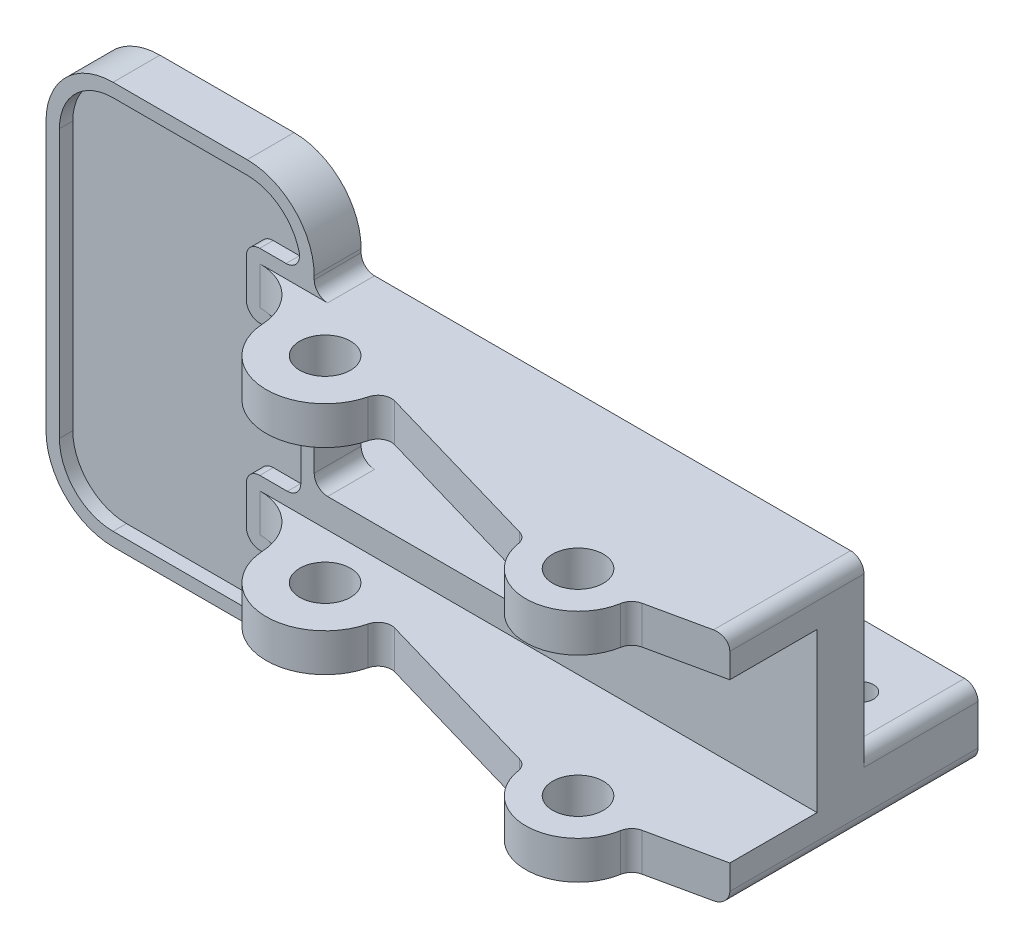
SolidWorks part; units mm, degrees
ref_plane "Front Plane" through (0, 0, 0) normal (0, 0, 1) x (1, 0, 0)
ref_plane "Top Plane" through (0, 0, 0) normal (0, 1, 0) x (1, 0, 0)
ref_plane "Right Plane" through (0, 0, 0) normal (1, 0, 0) x (0, 0, -1)
sketch "Sketch1" plane through (0, 0, 0) normal (0, 0, 1) x (1, 0, 0)
  line L1 (57.15, -22.225) -> (-57.15, -22.225)
  line L2 (57.15, -22.225) -> (57.15, 22.225)
  line L3 (57.15, 22.225) -> (-57.15, 22.225)
  line L4 (-57.15, -22.225) -> (-57.15, 22.225)
  line L5 (57.15, -22.225) -> (-57.15, 22.225) construction
  line L6 (57.15, 22.225) -> (-57.15, -22.225) construction
  point P0 (0, 0)
  dimension "D1" = 44.45
  dimension "D2" = 114.3
extrude "Boss-Extrude1" add sketch "Sketch1" along normal blind 62.23
sketch "Sketch2" plane through (0, 0, 62.23) normal (0, 0, 1) x (1, 0, 0)
  line L0 (-57.15, 22.225) -> (-57.15, -22.225) construction
  line L1 (57.15, -15.025) -> (-57.15, -15.025)
  line L2 (57.15, -15.025) -> (57.15, 15.025)
  line L3 (57.15, 15.025) -> (-57.15, 15.025)
  line L4 (-57.15, -15.025) -> (-57.15, 15.025)
  line L5 (57.15, -15.025) -> (-57.15, 15.025) construction
  line L6 (57.15, 15.025) -> (-57.15, -15.025) construction
  line L7 (57.15, 22.225) -> (-57.15, 22.225) construction
  point P0 (0, 0)
  dimension "D1" = 7.2
extrude "Cut-Extrude2" cut sketch "Sketch2" against normal blind 31.75
sketch "Sketch3" plane through (0, 0, 0) normal (0, 0, -1) x (-1, 0, 0)
  line L0 (-57.15, -22.225) -> (-57.15, 22.225) construction
  line L1 (57.15, 22.225) -> (-57.15, 22.225)
  line L2 (57.15, 22.225) -> (57.15, -9.525)
  line L3 (57.15, -9.525) -> (-57.15, -9.525)
  line L4 (-57.15, 22.225) -> (-57.15, -9.525)
  line L5 (57.15, -22.225) -> (-57.15, -22.225) construction
  dimension "D1" = 12.7
extrude "Cut-Extrude3" cut sketch "Sketch3" against normal blind 21.59
sketch "Sketch5" plane through (0, -22.225, 0) normal (0, -1, 0) x (1, 0, 0)
  line L0 (-3.81, 12.06) -> (46.99, 12.06) construction
  line L1 (57.15, 21.59) -> (-57.15, 21.59) construction
  line L2 (57.15, 62.23) -> (57.15, 0) construction
  circle A0 centre (-3.81, 12.06) radius 2.415
  circle A1 centre (46.99, 12.06) radius 2.415
  dimension "D3" = 4.83
  dimension "D4" = 10.16
  dimension "D1" = 9.53
  dimension "D2" = 50.8
extrude "Cut-Extrude4" cut sketch "Sketch5" against normal blind 25.4
sketch "Sketch6" plane through (0, 0, 21.59) normal (0, 0, -1) x (-1, 0, 0)
  line L0 (-49.405, -9.525) -> (6.225, -9.525) construction
  line L1 (-49.405, -9.525) -> (-49.405, -22.225) construction
  line L2 (6.225, -22.225) -> (6.225, -9.525) construction
  line L3 (-57.15, -9.525) -> (57.15, -9.525) construction
  line L6 (-29.083, 1.651) -> (-29.083, 6.477) construction
  line L7 (-22.4401, 6.477) -> (-22.4401, 1.651) construction
  line L8 (-29.083, 6.477) -> (-14.097, 6.477) construction
  line L9 (-19.177, 1.651) -> (-29.083, 1.651) construction
  circle A1 centre (-26.8605, 4.064) radius 2.2225
  dimension "D3" = 4.445
extrude "Cut-Extrude5" cut sketch "Sketch6" against normal blind 5.08
sketch "Sketch7" plane through (0, -22.225, 0) normal (0, -1, 0) x (1, 0, 0)
  line L0 (57.15, 62.23) -> (57.15, 0) construction
  line L1 (-57.15, 0) -> (57.15, 0) construction
  circle A0 centre (31.75, 50.36) radius 4.8
  circle A1 centre (-27.14, 39.37) radius 4.8
  dimension "D1" = 9.6
  dimension "D2" = 25.4
  dimension "D3" = 39.37
  dimension "D4" = 9.6
  dimension "D5" = 58.89
  dimension "D6" = 10.99
extrude "Cut-Extrude6" cut sketch "Sketch7" against normal up to surface (44.45 mm away) up to face at (0, 22.225, 41.91)
sketch "Sketch9" plane through (0, 0, 30.48) normal (0, 0, 1) x (1, 0, 0)
  line L5 (57.15, 15.025) -> (-57.15, 15.025) construction
  line L6 (-38.1, 15.025) -> (6.35, 15.025)
  line L7 (-38.1, 15.025) -> (-38.1, -15.025)
  line L8 (-38.1, -15.025) -> (6.35, -15.025)
  line L9 (6.35, 15.025) -> (6.35, -15.025)
  line L10 (-57.15, -15.025) -> (57.15, -15.025) construction
  line L11 (-57.15, 15.025) -> (-57.15, -15.025) construction
  line L12 (57.15, -15.025) -> (57.15, 15.025) construction
  dimension "D1" = 50.8
  dimension "25in" = 19.05
extrude "Cut-Extrude7" cut sketch "Sketch9" against normal through all both and the other way through all
sketch "Sketch16" plane through (0, -22.225, 0) normal (0, -1, 0) x (1, 0, 0)
  line L1 (-38.1, 30.48) -> (-57.15, 30.48) construction
  line L8 (-57.15, 62.23) -> (57.15, 62.23)
  line L9 (57.15, 62.23) -> (57.15, 47.0103)
  line L10 (57.15, 62.23) -> (57.15, 0) construction
  line L11 (-15.99, 39.37) -> (21.87, 50.36)
  line L12 (41.63, 50.36) -> (57.15, 47.0103)
  line L13 (-48.4121, 30.48) -> (-57.15, 30.48)
  line L15 (-57.15, 30.48) -> (-57.15, 62.23)
  arc A2 (41.63, 50.36) -> (21.87, 50.36) centre (31.75, 50.36) ccw
  arc A3 (-15.99, 39.37) -> (-38.2702, 40.0345) centre (-27.14, 39.37) ccw
  circle A4 centre (-27.14, 39.37) radius 4.8 construction
  circle A5 centre (31.75, 50.36) radius 4.8 construction
  arc A6 (-48.4121, 30.48) -> (-38.2702, 40.0345) centre (-48.4121, 40.64) ccw
  dimension "D1" = 6.35
  dimension "D2" = 5.08
  dimension "D3" = 10.16
extrude "Cut-Extrude8" cut sketch "Sketch16" against normal through all
fillet "Fillet1" radius 2.54 6 edges at (21.87, 18.625, 50.36) (41.63, -18.625, 50.36) (41.63, 18.625, 50.36) (-15.99, 18.625, 39.37) (-15.99, -18.625, 39.37) (21.87, -18.625, 50.36)
sketch "Sketch14" plane through (6.35, 0, 0) normal (-1, 0, 0) x (0, 0, 1)
  line L0 (0, -15.025) -> (30.48, -15.025) construction
  line L1 (21.59, -9.525) -> (0, -9.525)
  line L2 (21.59, -9.525) -> (21.59, -15.025)
  line L3 (21.59, -15.025) -> (0, -15.025)
  line L4 (0, -9.525) -> (0, -15.025)
extrude "Boss-Extrude2" add sketch "Sketch14" along normal up to next
sketch "Sketch17" plane through (0, 0, 21.59) normal (0, 0, 1) x (1, 0, 0)
  line L1 (6.35, -15.025) -> (-38.1, -15.025)
  line L2 (6.35, -15.025) -> (6.35, -9.525)
  line L3 (6.35, -9.525) -> (-38.1, -9.525)
  line L4 (-38.1, -15.025) -> (-38.1, -9.525)
extrude "Boss-Extrude3" add sketch "Sketch17" along normal up to surface (8.89 mm away) up to face at (31.75, 0, 30.48)
sketch "Sketch18" plane through (-57.15, 0, 0) normal (-1, 0, 0) x (0, 0, 1)
  line L0 (30.48, 22.225) -> (30.48, -22.225) construction
  line L1 (21.59, 22.225) -> (30.48, 22.225)
  line L2 (21.59, 22.225) -> (21.59, -22.225)
  line L3 (21.59, -22.225) -> (30.48, -22.225)
  line L4 (30.48, 22.225) -> (30.48, -22.225)
  line L5 (21.59, 22.225) -> (30.48, -22.225) construction
  line L6 (21.59, -22.225) -> (30.48, 22.225) construction
  line L7 (30.48, -22.225) -> (0, -22.225) construction
  line L8 (21.59, -9.525) -> (21.59, 22.225) construction
  line L9 (30.48, 22.225) -> (21.59, 22.225) construction
  point P0 (26.035, 0)
sketch "Sketch20" plane through (0, 0, 21.59) normal (0, 0, -1) x (-1, 0, 0)
  line L0 (38.1, 15.025) -> (38.1, -9.525) construction
  line L1 (38.1, 38.1) -> (88.9, 38.1)
  line L2 (38.1, 38.1) -> (38.1, -38.1)
  line L3 (38.1, -38.1) -> (88.9, -38.1)
  line L4 (88.9, 38.1) -> (88.9, -38.1)
  line L5 (38.1, 38.1) -> (88.9, -38.1) construction
  line L6 (38.1, -38.1) -> (88.9, 38.1) construction
  point P0 (63.5, 0)
  point P9 (88.9, 0)
  dimension "D1" = 76.2
  dimension "D2" = 50.8
extrude "Boss-Extrude5" add sketch "Sketch20" against normal up to vertex (8.89 mm away) up to point (-57.15, 22.225, 30.48)
fillet "Fillet4" radius 12.7 4 edges at (-38.1, -38.1, 26.035) (-88.9, -38.1, 26.035) (-88.9, 38.1, 26.035) (-38.1, 38.1, 26.035)
sketch "Sketch21" plane through (0, 0, 30.48) normal (0, 0, 1) x (1, 0, 0)
  line L0 (-40.64, -25.4) -> (-40.64, -24.765)
  line L16 (-50.9521, -12.485) -> (-40.64, -12.485)
  line L17 (-40.64, -12.485) -> (-40.64, -12.065)
  line L32 (-76.2, -35.56) -> (-50.8, -35.56)
  line L33 (-40.64, -25.4) -> (-40.64, -24.765)
  line L34 (-40.64, -24.765) -> (-50.9521, -24.765)
  line L35 (-50.9521, -24.765) -> (-50.9521, -12.485)
  line L36 (-50.9521, -12.485) -> (54.61, -12.485)
  line L37 (54.61, -12.485) -> (54.61, 12.485)
  line L38 (54.61, 12.485) -> (8.89, 12.485)
  line L39 (8.89, 12.485) -> (8.89, -12.065)
  line L40 (8.89, -12.065) -> (-40.64, -12.065)
  line L41 (-40.64, -12.065) -> (-40.64, 12.485)
  line L42 (-40.64, 12.485) -> (-50.9521, 12.485)
  line L43 (-50.9521, 12.485) -> (-50.9521, 24.765)
  line L44 (-50.9521, 24.765) -> (-40.64, 24.765)
  line L45 (-40.64, 24.765) -> (-40.64, 25.4)
  line L46 (-50.8, 35.56) -> (-76.2, 35.56)
  line L47 (-86.36, 25.4) -> (-86.36, -25.4)
  line L48 (-76.2, -35.56) -> (-50.8, -35.56)
  line L50 (-40.64, -24.765) -> (-50.9521, -24.765)
  line L51 (-50.9521, -24.765) -> (-50.9521, -12.485)
  line L57 (-40.64, -12.065) -> (-40.64, 12.485)
  line L58 (-40.64, 12.485) -> (-50.9521, 12.485)
  line L59 (-50.9521, 12.485) -> (-50.9521, 24.765)
  line L60 (-50.9521, 24.765) -> (-40.64, 24.765)
  line L61 (-40.64, 24.765) -> (-40.64, 25.4)
  line L62 (-50.8, 35.56) -> (-76.2, 35.56)
  line L63 (-86.36, 25.4) -> (-86.36, -25.4)
  arc A8 (-50.8, -35.56) -> (-40.64, -25.4) centre (-50.8, -25.4) ccw
  arc A9 (-40.64, 25.4) -> (-50.8, 35.56) centre (-50.8, 25.4) ccw
  arc A10 (-76.2, 35.56) -> (-86.36, 25.4) centre (-76.2, 25.4) ccw
  arc A11 (-86.36, -25.4) -> (-76.2, -35.56) centre (-76.2, -25.4) ccw
  arc A12 (-50.8, -35.56) -> (-40.64, -25.4) centre (-50.8, -25.4) ccw
  arc A13 (-40.64, 25.4) -> (-50.8, 35.56) centre (-50.8, 25.4) ccw
  arc A14 (-76.2, 35.56) -> (-86.36, 25.4) centre (-76.2, 25.4) ccw
  arc A15 (-86.36, -25.4) -> (-76.2, -35.56) centre (-76.2, -25.4) ccw
  dimension "D1" = 2.54
extrude "Cut-Extrude10" cut sketch "Sketch21" against normal blind 2.54
fillet "Fillet5" radius 2.54 12 edges at (-40.64, -24.765, 29.21) (-50.9521, -24.765, 29.21) (-50.9521, -12.485, 29.21) (-40.64, -12.485, 29.21) (-40.64, 12.485, 29.21) (-50.9521, 12.485, 29.21) (-50.9521, 24.765, 29.21) (-40.64, 24.765, 29.21) (57.15, -22.225, 23.5051) (57.15, 22.225, 34.3001) (-38.1, 22.225, 26.035) (-38.1, -22.225, 26.035)
fillet "Fillet6" radius 2.54 7 edges at (6.35, -9.525, 26.035) (6.35, 15.025, 26.035) (-38.1, 15.025, 26.035) (-38.1, -9.525, 26.035) (57.15, -9.525, 10.795) (-57.15, -9.525, 10.795) (-57.15, -22.225, 10.795)
